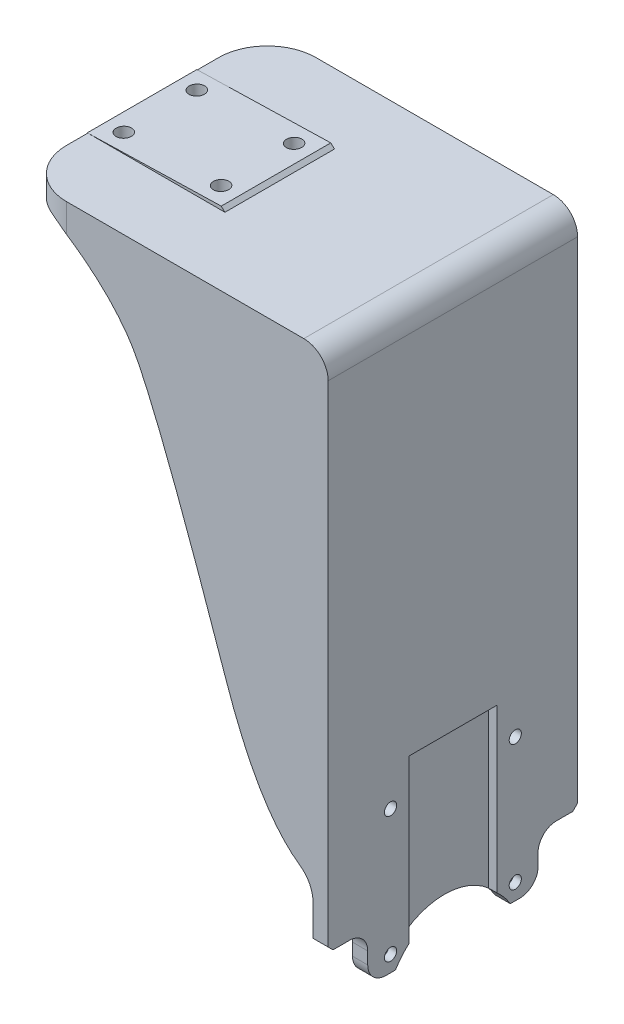
SolidWorks part; units mm, degrees
ref_plane "前视基准面" through (0, 0, 0) normal (0, 0, 1) x (1, 0, 0)
ref_plane "上视基准面" through (0, 0, 0) normal (0, 1, 0) x (1, 0, 0)
ref_plane "右视基准面" through (0, 0, 0) normal (1, 0, 0) x (0, 0, -1)
other "Configuration Table"
sketch "草图1" plane through (0, 0, 0) normal (0, 1, 0) x (1, 0, 0)
  line L0 (-22.5, 11.2328) -> (-22.5, -19.6928) construction
  line L1 (-25.5, 20.5) -> (25.5, 20.5)
  line L2 (-25.5, 20.5) -> (-25.5, -20.5)
  line L3 (-25.5, -20.5) -> (25.5, -20.5)
  line L4 (25.5, 20.5) -> (25.5, -20.5)
  line L5 (-25.5, 20.5) -> (25.5, -20.5) construction
  line L6 (-25.5, -20.5) -> (25.5, 20.5) construction
  line L7 (-17.7344, 0) -> (22.5332, 0) construction
  point P0 (0, 0)
  dimension "D1" = 41
  dimension "D2" = 3
  dimension "D5" = 51
extrude "凸台-拉伸1" add sketch "草图1" along normal blind 3.4
sketch "草图2" plane through (25.5, 0, 0) normal (1, 0, 0) x (0, 0, -1)
  line L0 (-20.5, 0) -> (20.5, 0)
  line L1 (20.5, 0) -> (20.5, -90)
  line L2 (20.5, -90) -> (9.4381, -90)
  line L3 (-20.5, -90) -> (-20.5, 0)
  line L4 (0, 12.0877) -> (0, -84.65) construction
  line L5 (-30.0581, -77) -> (27.3842, -77) construction
  line L6 (-9.4381, -90) -> (-20.5, -90)
  line L7 (0, -64) -> (0, -84.8169) construction
  circle A0 centre (-10.25, -87.35) radius 1
  circle A1 centre (10.25, -87.35) radius 1
  circle A2 centre (10.25, -66.65) radius 1
  circle A3 centre (-10.25, -66.65) radius 1
  arc A4 (9.4381, -90) -> (-9.4381, -90) centre (0, -95.65) ccw
  dimension "D3" = 2
  dimension "D4" = 20.5
  dimension "D5" = 20.7
  dimension "D6" = 8.3
  dimension "D7" = 11
  dimension "D1" = 90
  dimension "D2" = 13
extrude "凸台-拉伸2" add sketch "草图2" against normal blind 2.5
sketch "草图3" plane through (25.5, 0, 0) normal (1, 0, 0) x (0, 0, -1)
  line L0 (0, 9.7576) -> (0, -76.6891) construction
  line L5 (-7.25, -60.65) -> (-7.25, -106.3874)
  line L6 (-7.25, -106.3874) -> (7.25, -106.3874)
  line L7 (-7.25, -60.65) -> (7.25, -60.65)
  line L8 (7.25, -60.65) -> (7.25, -106.3874)
  circle A0 centre (-10.25, -66.65) radius 1 construction
  point P10 (0, -60.65)
  point P11 (0, -106.3874)
  dimension "D2" = 6
  dimension "D1" = 3
extrude "切除-拉伸1" cut sketch "草图3" against normal blind 1.4
sketch "草图5" plane through (0, 0, -20.5) normal (0, 0, -1) x (-1, 0, 0)
  line L0 (-25.5, 3.4) -> (19.5, 3.4)
  line L1 (-25.5, -73.0752) -> (-25.5, 3.4)
  line L2 (19.5, 3.4) -> (19.5, 0)
  line L3 (-25.5, -73.0752) -> (-23, -73.0752)
  line L5 (-25.5, 3.4) -> (-25.5, -90) construction
  line L6 (25.5, 3.4) -> (25.5, 0) construction
  spline S0 degree 2 poles (19.5, 0) (10.6712, -5.3693) (2.7794, -18.1934) (-14.9584, -69.6831) (-23, -73.0752) knots 0 0 0 0.396049 0.78858 1 1 1
  point P7 (-25.5, 3.4)
  point P8 (-8.235, -54.1299)
  point P10 (-8.7491, -51.6585)
  dimension "D1" = 6
extrude "凸台-拉伸4" add sketch "草图5" against normal blind 2
mirror "镜向3" about plane through (0, 0, 0) normal (0, 0, 1) of "凸台-拉伸4"
fillet "圆角1" radius 8 2 edges at (-25.5, 1.7, -20.5) (-25.5, 1.7, 20.5)
fillet "圆角2" radius 4 2 edges at (23, 0, 0) (25.5, 3.4, 0)
sketch "草图6" plane through (23, 0, 0) normal (-1, 0, 0) x (0, 0, 1)
  circle A0 centre (10.25, -87.35) radius 2
  circle A1 centre (-10.25, -87.35) radius 2
  dimension "D1" = 4
  dimension "D2" = 4
extrude "切除-拉伸2" cut sketch "草图6" against normal blind 1.2
sketch "草图8" plane through (25.5, 0, 0) normal (1, 0, 0) x (0, 0, -1)
  line L0 (14, -102.818) -> (14, -82)
  line L1 (14, -82) -> (23.4685, -82)
  line L2 (23.4685, -82) -> (23.4685, -110.0082)
  line L3 (23.4685, -110.0082) -> (-23.4685, -110.0082)
  line L4 (-23.4685, -82) -> (-23.4685, -110.0082)
  line L5 (0, -27.3846) -> (0, -80.1854) construction
  line L6 (-14, -82) -> (-23.4685, -82)
  line L7 (-14, -102.818) -> (-14, -82)
  line L8 (-14, -102.818) -> (14, -102.818)
  line L9 (9.4381, -90) -> (20.5, -90) construction
  point P9 (0, -110.0082)
  dimension "D1" = 28
  dimension "D2" = 8
extrude "切除-拉伸3" cut sketch "草图8" against normal blind 4
fillet "圆角3" radius 3 4 edges at (24.25, -90, -14) (24.25, -82, -14) (24.25, -82, 14) (24.25, -90, 14)
sketch "草图9" plane through (23, 0, 0) normal (-1, 0, 0) x (0, 0, 1)
  line L0 (0, 14.9311) -> (0, -25.9548) construction
  circle A0 centre (10.25, -66.65) radius 2
  circle A1 centre (-10.25, -66.65) radius 2
  dimension "D1" = 4
extrude "切除-拉伸4" cut sketch "草图9" against normal blind 0.8
ref_plane "基准面1" through (-0.0175, 0.6673, 0) normal (0.0262, -0.9997, 0) x (0, 0, 1)
chamfer "倒角1" distance 0.8 angle 45 2 edges at (24.25, -82, 20.5) (24.25, -82, -20.5)
fillet "圆角4" radius 4 6 edges at (-0.25, 0, -18.5) (21.8284, -1.1716, -18.5) (-0.25, 0, 18.5) (21.8284, -1.1716, 18.5) (23, -38.5376, -18.5) (23, -38.5376, 18.5)
fillet "圆角5" radius 5 4 edges at (23, -73.0752, 17.5) (23, -73.0752, -17.5) (-19.5, 0, 17.373) (-19.5, 0, -17.373)
sketch "草图11" plane through (-0.0175, 0.6673, 0) normal (0.0262, -0.9997, 0) x (0, 0, 1)
  line L0 (0, 35.0902) -> (0, -5.4018) construction
  line L1 (-9, 25.4913) -> (9, 25.4913)
  line L2 (-9, 25.4913) -> (-9, 3.4913)
  line L3 (-9, 3.4913) -> (9, 3.4913)
  line L4 (9, 25.4913) -> (9, 3.4913)
  line L5 (-9, 25.4913) -> (9, 3.4913) construction
  line L6 (-9, 3.4913) -> (9, 25.4913) construction
  line L7 (-12.5, 25.4913) -> (12.5, 25.4913) construction
  point P0 (0, 14.4913)
  point P8 (0, 12.5946)
  dimension "D1" = 18
  dimension "D2" = 22
extrude "凸台-拉伸5" add sketch "草图11" along normal blind 1
ref_plane "基准面2" through (-0.1064, 4.065, 0) normal (0.0262, -0.9997, 0) x (-0.9997, -0.0262, 0)
sketch "草图12" plane through (-0.1064, 4.065, 0) normal (0.0262, -0.9997, 0) x (-0.9997, -0.0262, 0)
  line L4 (3.4913, -9) -> (25.4913, -9)
  line L5 (25.4913, -9) -> (25.4913, 9)
  line L6 (25.4913, 9) -> (3.4913, 9)
  line L7 (3.4913, 9) -> (3.4913, -9)
  line L8 (3.4913, -9) -> (25.4913, -9)
  line L9 (25.4913, -9) -> (25.4913, 9)
  line L10 (25.4913, 9) -> (3.4913, 9)
  line L11 (3.4913, 9) -> (3.4913, -9)
  dimension "D1" = 0
extrude "凸台-拉伸6" add sketch "草图12" along normal blind 1
sketch "草图13" plane through (0.0087, -0.3324, 0) normal (0.0262, -0.9997, 0) x (0.9997, 0.0262, 0)
  line L0 (8.0225, 0) -> (-29.4849, 0) construction
  line L1 (-14.4913, 12.2938) -> (-14.4913, -13.2045) construction
  line L2 (-25.4913, 9) -> (-25.4913, -9) construction
  circle A0 centre (-22.4913, 6) radius 1.25
  circle A1 centre (-22.4913, -6) radius 1.25
  circle A2 centre (-6.4913, -6) radius 1.25
  circle A3 centre (-6.4913, 6) radius 1.25
  point P7 (-14.573, 12.2938)
  dimension "D1" = 2.5
  dimension "D2" = 12
  dimension "D3" = 16
  dimension "D4" = 3
extrude "切除-拉伸5" cut sketch "草图13" against normal through all
sketch "草图14" plane through (0.0087, -0.3324, 0) normal (0.0262, -0.9997, 0) x (-0.9997, -0.0262, 0)
  circle A0 centre (22.4913, -6) radius 2.5
  circle A1 centre (6.4913, -6) radius 2.5
  circle A2 centre (6.4913, 6) radius 2.5
  circle A3 centre (22.4913, 6) radius 2.5
  dimension "D3" = 5
  dimension "D1" = 2
  dimension "D2" = 2
extrude "切除-拉伸6" cut sketch "草图14" against normal blind 1
chamfer "倒角2" distance 0.6 angle 45 1 edges at (-3.5815, 3.4, 0) first distance on face at (-3.589, 3.6868, 0)
ref_plane "基准面3" through (0, -40, 0) normal (0, -1, 0) x (-1, 0, 0)
sketch "草图15" plane through (0, -40, 0) normal (0, -1, 0) x (-1, 0, 0)
  line L0 (-20.8429, -20.5) -> (17.5, -20.5) construction
  line L1 (-25.5, 20.5) -> (-5.5, 20.5)
  line L2 (-25.5, 20.5) -> (-25.5, -20.5)
  line L3 (-25.5, -20.5) -> (-5.5, -20.5)
  line L4 (-5.5, 20.5) -> (-5.5, -20.5)
  dimension "D1" = 20
extrude "凸台-拉伸7" add sketch "草图15" against normal blind 2
